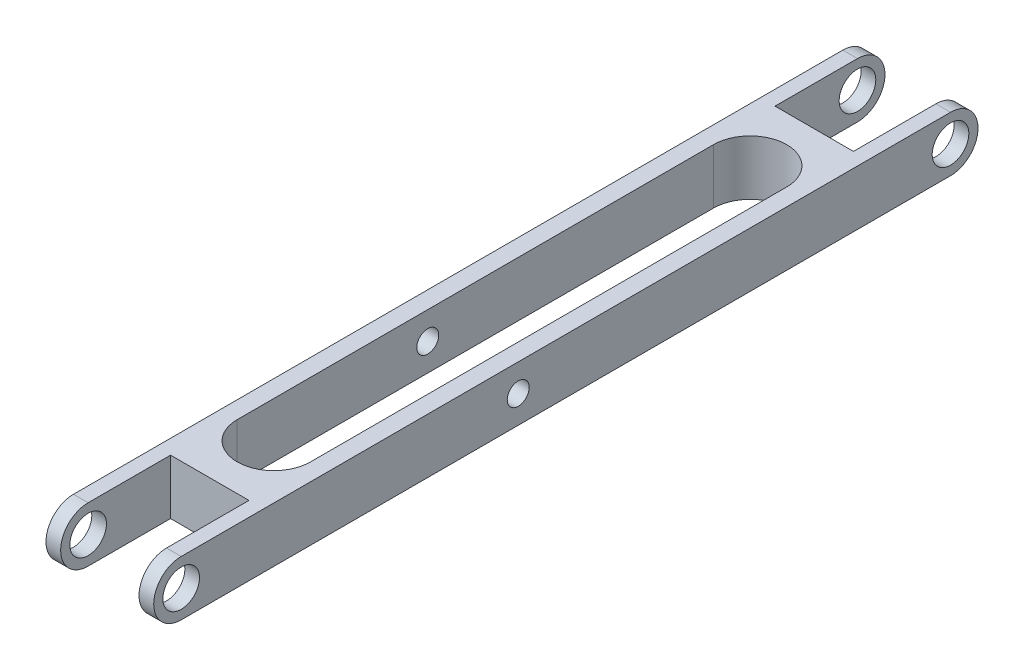
SolidWorks part; units mm, degrees
material "ABS"
ref_plane "前视基准面" through (0, 0, 0) normal (0, 0, 1) x (1, 0, 0)
ref_plane "上视基准面" through (0, 0, 0) normal (0, 1, 0) x (1, 0, 0)
ref_plane "右视基准面" through (0, 0, 0) normal (1, 0, 0) x (0, 0, -1)
sketch "草图2" plane through (0, 0, 0) normal (1, 0, 0) x (0, 0, -1)
  line L0 (-105, 7.5) -> (-105, -7.5) construction
  line L1 (-105, -7.5) -> (105, -7.5)
  line L3 (-105, 7.5) -> (105, 7.5)
  line L5 (-105, -7.5) -> (105, 7.5) construction
  line L6 (-105, 7.5) -> (105, -7.5) construction
  line L7 (105, 7.5) -> (105, -7.5) construction
  arc A0 (-105, 7.5) -> (-105, -7.5) centre (-105, 0) ccw
  arc A1 (105, 7.5) -> (105, -7.5) centre (105, 0) cw
  point P0 (0, 0)
  dimension "D1" = 15
  dimension "D2" = 210
extrude "凸台-拉伸1" add sketch "草图2" along normal blind 29.4
sketch "草图3" plane through (0, 7.5, 0) normal (0, 1, 0) x (1, 0, 0)
  line L1 (4, -112.5) -> (4, -82.5)
  line L2 (0, -112.5) -> (29.4, -112.5) construction
  line L3 (4, -82.5) -> (25.4, -82.5)
  line L4 (25.4, -82.5) -> (25.4, -112.5)
  line L5 (25.4, -112.5) -> (4, -112.5)
  line L6 (0, 105) -> (0, -105) construction
  line L7 (29.4, 105) -> (29.4, -105) construction
  line L10 (4, 112.5) -> (25.4, 112.5)
  line L14 (4, 112.5) -> (4, 82.5)
  line L15 (4, 82.5) -> (25.4, 82.5)
  line L16 (25.4, 82.5) -> (25.4, 112.5)
  line L17 (29.4, 105) -> (0, 105) construction
  dimension "D1" = 4
  dimension "D2" = 4
  dimension "D3" = 30
  dimension "D4" = 21.4
  dimension "D5" = 30
  dimension "D6" = 7.5
  dimension "D7" = 4
extrude "切除-拉伸1" cut sketch "草图3" against normal through all
sketch "草图4" plane through (29.4, 0, 0) normal (1, 0, 0) x (0, 0, -1)
  circle A0 centre (-105, 0) radius 5
  circle A1 centre (105, 0) radius 5
  dimension "D1" = 10
  dimension "D2" = 10
extrude "切除-拉伸2" cut sketch "草图4" against normal through all
sketch "草图5" plane through (0, -7.5, 0) normal (0, -1, 0) x (1, 0, 0)
  line L0 (14.7, 65) -> (14.7, -65) construction
  line L1 (24.7, 65) -> (24.7, -65)
  line L2 (4.7, 65) -> (4.7, -65)
  line L3 (0, 0) -> (14.7, 0) construction
  line L4 (0, 105) -> (0, -105) construction
  arc A0 (24.7, 65) -> (4.7, 65) centre (14.7, 65) ccw
  arc A1 (4.7, -65) -> (24.7, -65) centre (14.7, -65) ccw
  point P2 (14.7, 0)
  dimension "D1" = 20
  dimension "D2" = 14.7
  dimension "D3" = 130
extrude "切除-拉伸3" cut sketch "草图5" against normal through all
sketch "草图6" plane through (0, 0, 0) normal (-1, 0, 0) x (0, 0, 1)
  line L0 (13, 0) -> (0, 0) construction
  circle A1 centre (13, 0) radius 3
  circle A3 centre (105, 0) radius 5 construction
  dimension "D1" = 92
  dimension "D2" = 6
extrude "切除-拉伸4" cut sketch "草图6" against normal through all
